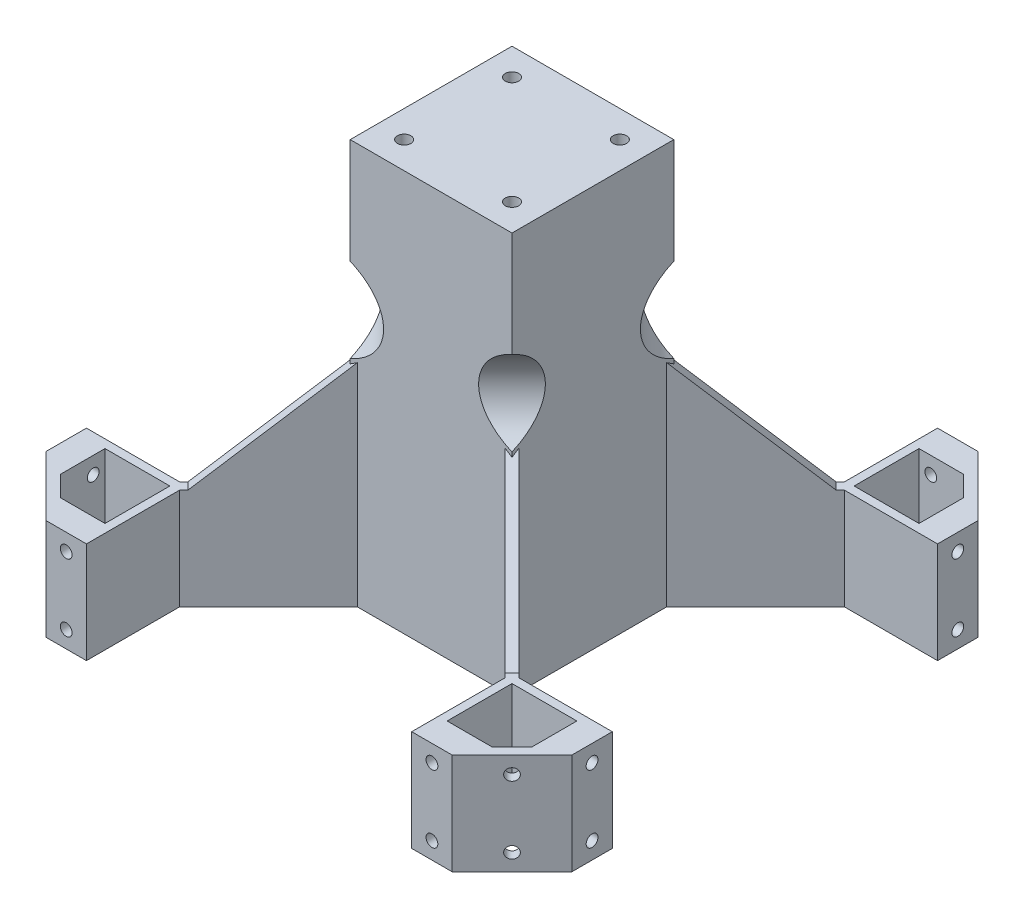
SolidWorks part; units mm, degrees
ref_plane "Front Plane" through (0, 0, 0) normal (0, 0, 1) x (1, 0, 0)
ref_plane "Top Plane" through (0, 0, 0) normal (0, 1, 0) x (1, 0, 0)
ref_plane "Right Plane" through (0, 0, 0) normal (1, 0, 0) x (0, 0, -1)
sketch "Sketch1" plane through (0, 0, 0) normal (0, 1, 0) x (1, 0, 0)
  line L0 (0, 0) -> (0, -80) construction
  line L1 (0, 0) -> (80, 0) construction
  line L2 (0, -78) -> (59.25, -78) construction
  line L7 (59.25, -78) -> (59.25, -82) construction
  line L8 (78, 0) -> (78, -59.25) construction
  line L9 (78, -59.25) -> (82, -59.25) construction
  line L10 (48.25, -78) -> (48.25, -50.3713)
  line L11 (48.25, -78) -> (60.25, -78)
  line L12 (60.25, -78) -> (69.125, -69.125)
  line L15 (0, 0) -> (110.9515, -110.9515) construction
  line L16 (48.25, -50.3713) -> (20.1525, -22.2739)
  line L18 (50.75, -50.75) -> (50.75, -70)
  line L19 (50.75, -70) -> (64.0074, -70)
  line L20 (64.0074, -70) -> (67.0037, -67.0037)
  line L21 (67.0037, -67.0037) -> (69.125, -69.125)
  line L22 (50.75, -50.75) -> (21.2132, -21.2132)
  line L23 (21.2132, -21.2132) -> (20.1525, -22.2739)
  circle A0 centre (0, -80) radius 47.5 construction
  circle A1 centre (0, -80) radius 55 construction
  circle A2 centre (80, 0) radius 55 construction
  circle A3 centre (80, 0) radius 47.5 construction
  point P12 (54.25, -78)
  point P14 (78, -54.25)
  dimension "D1" = 95
  dimension "D2" = 110
  dimension "D3" = 110
  dimension "D4" = 80
  dimension "D5" = 2
  dimension "D6" = 2
  dimension "D7" = 4
  dimension "D8" = 4
  dimension "D9" = 59.25
  dimension "D10" = 54.25
  dimension "D11" = 54.25
  dimension "D12" = 45
  dimension "D13" = 2.5
  dimension "D14" = 12
  dimension "D15" = 8
  dimension "D16" = 3
  dimension "D17" = 1.5
  dimension "D18" = 30
extrude "Boss-Extrude1" add sketch "Sketch1" along normal blind 30
sketch "Sketch2" plane through (0, 0, 78) normal (0, 0, 1) x (1, 0, 0)
  line L0 (0, 0) -> (0, 86.05) construction
  line L1 (48.25, 0) -> (60.25, 0) construction
  circle A0 centre (54.25, 5) radius 1.75
  circle A1 centre (54.25, 25) radius 1.75
  dimension "D2" = 3.5
  dimension "D1" = 54.25
  dimension "D3" = 20
  dimension "D4" = 5
extrude "Cut-Extrude1" cut sketch "Sketch2" against normal up to surface (8 mm away) up to face at (57.3787, 15, 70)
ref_axis "Axis1" through (0, 31.5, 0) along (0, -1, 0)
mirror "Mirror1" about plane through (50.75, 30, 50.75) normal (-0.7071, 0, 0.7071) of "Boss-Extrude1", "Cut-Extrude1"
sketch "Sketch5" plane through (69.125, 0, 69.125) normal (0.7071, 0, 0.7071) x (0.7071, 0, -0.7071)
  line L0 (-12.5511, 0) -> (12.5511, 0) construction
  line L1 (0, 0) -> (0, 47.4993) construction
  circle A0 centre (0, 25) radius 1.75
  circle A1 centre (0, 5) radius 1.75
  dimension "D3" = 3.5
  dimension "D1" = 20
  dimension "D2" = 5
extrude "Cut-Extrude2" cut sketch "Sketch5" against normal up to surface (3 mm away) up to face at (67.0037, 15, 67.0037)
sketch "Sketch3" plane through (-1.0607, 0, 1.0607) normal (-0.7071, 0, 0.7071) x (0.7071, 0, 0.7071)
  line L0 (30, 30) -> (30, 65)
  line L1 (30, 65) -> (68, 30)
  line L2 (30, 30) -> (69.7358, 30) construction
  line L3 (68, 30) -> (30, 30)
  dimension "D1" = 38
  dimension "D2" = 35
extrude "Boss-Extrude2" add sketch "Sketch3" against normal up to surface (3 mm away) up to face at (36.3226, 15, 34.2013)
pattern_circular "CirPattern5" count 4 every 90 about axis through (0, 31.5, 0) along (0, -1, 0) of bodies 108 102
sketch "Sketch4" plane through (0, 0, 0) normal (0, -1, 0) x (1, 0, 0)
  line L1 (-24, -24) -> (24, -24)
  line L2 (-24, -24) -> (-24, 24)
  line L3 (-24, 24) -> (24, 24)
  line L4 (24, -24) -> (24, 24)
  line L5 (-24, -24) -> (24, 24) construction
  line L6 (-24, 24) -> (24, -24) construction
  line L7 (-21, -21) -> (21, -21)
  line L8 (-21, -21) -> (-21, 21)
  line L9 (-21, 21) -> (21, 21)
  line L10 (21, -21) -> (21, 21)
  line L11 (-21, -21) -> (21, 21) construction
  line L12 (-21, 21) -> (21, -21) construction
  point P0 (0, 0)
  point P6 (0, 0)
  dimension "D1" = 48
  dimension "D2" = 3
extrude "Boss-Extrude3" add sketch "Sketch4" against normal blind 115
sketch "Sketch6" plane through (0, 115, 0) normal (0, 1, 0) x (1, 0, 0)
  line L5 (24, -24) -> (24, 24)
  line L6 (24, 24) -> (-24, 24)
  line L7 (-24, 24) -> (-24, -24)
  line L8 (-24, -24) -> (24, -24)
  line L9 (24, -24) -> (24, 24)
  line L10 (24, 24) -> (-24, 24)
  line L11 (-24, 24) -> (-24, -24)
  line L12 (-24, -24) -> (24, -24)
  dimension "D1" = 0
extrude "Boss-Extrude4" add sketch "Sketch6" along normal blind 4
sketch "Sketch7" plane through (0, 119, 0) normal (0, 1, 0) x (1, 0, 0)
  line L1 (16, -16) -> (-16, -16) construction
  line L2 (16, -16) -> (16, 16) construction
  line L3 (16, 16) -> (-16, 16) construction
  line L4 (-16, -16) -> (-16, 16) construction
  line L5 (16, -16) -> (-16, 16) construction
  line L6 (16, 16) -> (-16, -16) construction
  circle A0 centre (16, 16) radius 2
  circle A1 centre (-16, 16) radius 2
  circle A2 centre (-16, -16) radius 2
  circle A3 centre (16, -16) radius 2
  point P8 (0, 0)
  dimension "D1" = 4
  dimension "D2" = 32
  dimension "D3" = 32
extrude "Cut-Extrude3" cut sketch "Sketch7" against normal up to surface (4 mm away) up to face at (0, 115, 0)
ref_plane "Plane1" through (0, 0, 0) normal (0.7071, 0, 0.7071) x (0.7071, 0, -0.7071)
sketch "Sketch8" plane through (0, 0, 0) normal (0.7071, 0, 0.7071) x (0.7071, 0, -0.7071)
  line L0 (-33.9411, 119) -> (-33.9411, 61.37) construction
  line L1 (-29.7778, 62.7516) -> (-48.454, 62.7516) construction
  line L2 (-26.9411, 74.4153) -> (-26.9411, 72.351) construction
  line L3 (-33.9411, 87.7516) -> (-33.9411, 62.7516)
  arc A0 (-33.9411, 62.7516) -> (-33.9411, 87.7516) centre (-41.6018, 75.2516) ccw
  point P10 (-33.9411, 62.7516)
  point P11 (0, 0)
  point P12 (0, 0)
  dimension "D2" = 25
  dimension "D3" = 7
extrude "Cut-Extrude4" cut sketch "Sketch8" against normal through all both and the other way through all
sketch "Sketch9" plane through (0, 0, 0) normal (0.7071, 0, 0.7071) x (0.7071, 0, -0.7071)
  line L0 (-29.6985, 83.81) -> (-29.6985, 88.2981)
  line L1 (-29.6985, 66.6932) -> (-29.6985, 62.2051)
  arc A1 (-33.9411, 62.7516) -> (-33.9411, 87.7516) centre (-41.6018, 75.2516) ccw construction
  arc A2 (-32.3735, 60.1937) -> (-32.3735, 90.3095) centre (-41.6018, 75.2516) ccw
  arc A3 (-29.6985, 62.2051) -> (-29.6985, 88.2981) centre (-41.6018, 75.2516) ccw
  arc A4 (-29.6985, 66.6932) -> (-29.6985, 83.81) centre (-41.6018, 75.2516) ccw
  point P3 (-29.6985, 63.1774)
  point P5 (-29.6985, 63.1022)
  dimension "D1" = 3
extrude "Boss-Extrude5" add sketch "Sketch9" along normal up to next and the other way up to next
pattern_circular "CirPattern6" count 4 every 90 about axis through (0, 31.5, 0) along (0, -1, 0) of "Cut-Extrude4", "Boss-Extrude5"
